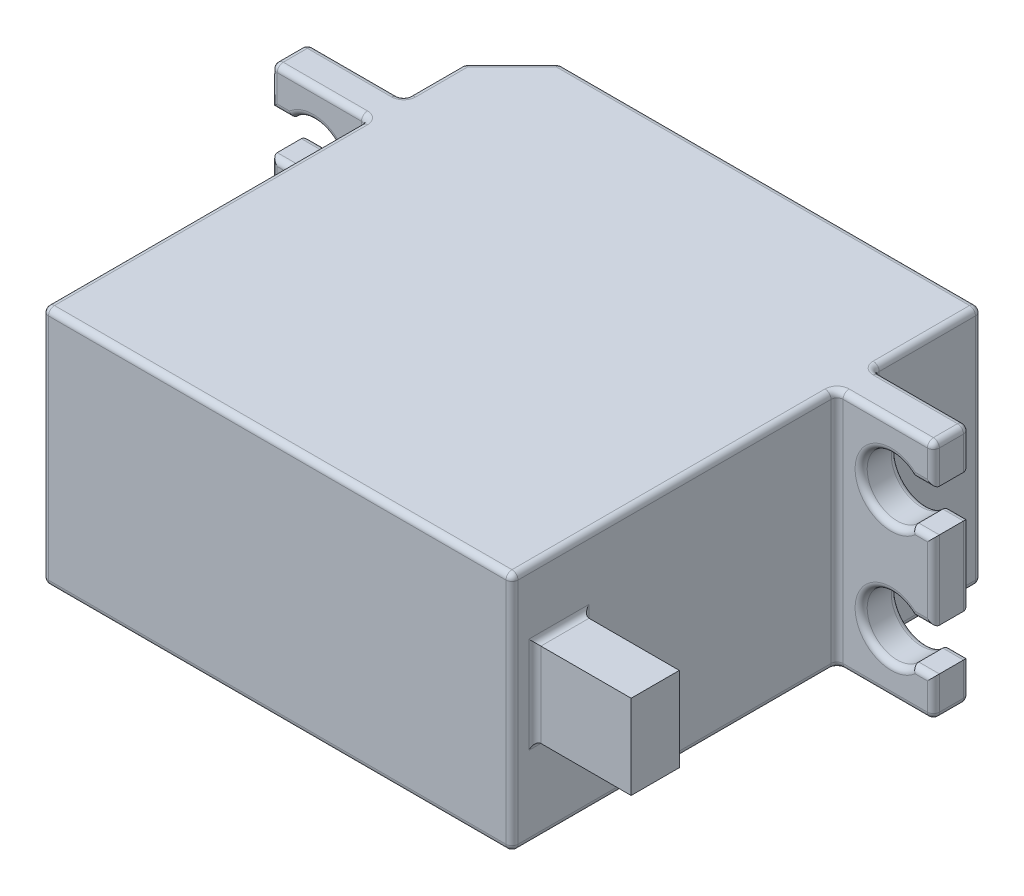
SolidWorks part; units mm, degrees
ref_plane "Plan de face" through (0, 0, 0) normal (0, 0, 1) x (1, 0, 0)
ref_plane "Plan de dessus" through (0, 0, 0) normal (0, 1, 0) x (1, 0, 0)
ref_plane "Plan de droite" through (0, 0, 0) normal (1, 0, 0) x (0, 0, -1)
sketch "Esquisse1" plane through (0, 0, 0) normal (0, 1, 0) x (1, 0, 0)
  line L0 (0, 35) -> (4, 39)
  line L1 (0, 0) -> (39, 0)
  line L2 (0, 0) -> (0, 35)
  line L3 (4, 39) -> (39, 39)
  line L4 (39, 0) -> (39, 39)
  dimension "D1" = 39
  dimension "D2" = 39
extrude "Boss.-Extru.1" add sketch "Esquisse1" along normal blind 20
sketch "Esquisse2" plane through (0, 0, 0) normal (-1, 0, 0) x (0, 0, 1)
  line L0 (-35, 0) -> (0, 0) construction
  line L1 (-30, 0) -> (-27, 0)
  line L2 (-30, 0) -> (-30, 20)
  line L3 (-30, 20) -> (-27, 20)
  line L4 (-27, 0) -> (-27, 20)
  line L5 (-35, 20) -> (0, 20) construction
  line L6 (0, 20) -> (0, 0) construction
  dimension "D1" = 3
  dimension "D2" = 27
extrude "Boss.-Extru.2" add sketch "Esquisse2" along normal blind 8 and the other way blind 47
sketch "Esquisse3" plane through (0, 0, -30) normal (0, 0, -1) x (-1, 0, 0)
  line L0 (8, 20) -> (8, 0) construction
  line L1 (0, 0) -> (8, 0) construction
  line L2 (0, 20) -> (8, 20) construction
  line L4 (6.2854, 3.25) -> (8, 3.25)
  line L5 (6.2854, 13.25) -> (8, 13.25)
  line L6 (6.2854, 6.75) -> (8, 6.75)
  line L7 (8, 3.25) -> (8, 6.75)
  line L9 (6.2854, 16.75) -> (8, 16.75)
  line L10 (8, 13.25) -> (8, 16.75)
  arc A0 (6.2854, 6.75) -> (6.2854, 3.25) centre (4.5, 5) ccw
  arc A1 (6.2854, 16.75) -> (6.2854, 13.25) centre (4.5, 15) ccw
  dimension "D1" = 5
  dimension "D2" = 5
  dimension "D3" = 3.5
  dimension "D4" = 3.5
  dimension "D5" = 5
  dimension "D6" = 5
  dimension "D8" = 1.75
  dimension "D9" = 1.75
extrude "Enlèv. mat.-Extru.1" cut sketch "Esquisse3" against normal blind 8
sketch "Esquisse4" plane through (0, 0, -30) normal (0, 0, -1) x (-1, 0, 0)
  line L0 (-47, 20) -> (-39, 20) construction
  line L1 (-47, 0) -> (-39, 0) construction
  line L2 (-47, 20) -> (-47, 0) construction
  line L3 (-39, 20) -> (-39, 0) construction
  line L4 (-47, 3.25) -> (-45.2854, 3.25)
  line L5 (-47, 3.25) -> (-47, 6.75)
  line L6 (-47, 6.75) -> (-45.2854, 6.75)
  line L8 (-45.2854, 13.25) -> (-47, 13.25)
  line L10 (-45.2854, 16.75) -> (-47, 16.75)
  line L11 (-47, 13.25) -> (-47, 16.75)
  arc A0 (-45.2854, 3.25) -> (-45.2854, 6.75) centre (-43.5, 5) ccw
  arc A1 (-45.2854, 13.25) -> (-45.2854, 16.75) centre (-43.5, 15) ccw
  dimension "D1" = 5
  dimension "D2" = 5
  dimension "D3" = 5
  dimension "D4" = 5
  dimension "D5" = 3.5
  dimension "D6" = 3.5
  dimension "D8" = 1.75
  dimension "D9" = 1.75
extrude "Enlèv. mat.-Extru.2" cut sketch "Esquisse4" against normal blind 8
sketch "Esquisse6" plane through (0, 0, -39) normal (0, 0, -1) x (-1, 0, 0)
  line L0 (-39, 20) -> (-4, 20) construction
  line L1 (-39, 20) -> (-39, 0) construction
  circle A0 centre (-29, 10) radius 6
  dimension "D1" = 12
  dimension "D2" = 10
  dimension "D3" = 10
extrude "Boss.-Extru.3" add sketch "Esquisse6" along normal blind 1
sketch "Esquisse7" plane through (0, 0, -40) normal (0, 0, -1) x (-1, 0, 0)
  line L0 (-39, 20) -> (-4, 20) construction
  line L1 (-39, 20) -> (-39, 0) construction
  circle A0 centre (-29, 10) radius 3
  dimension "D1" = 10
  dimension "D2" = 10
  dimension "D3" = 6
extrude "Boss.-Extru.4" add sketch "Esquisse7" along normal blind 4
sketch "Esquisse8" plane through (39, 0, 0) normal (1, 0, 0) x (0, 0, -1)
  line L1 (5.8966, 7.3034) -> (1.8966, 7.3034)
  line L2 (5.8966, 7.3034) -> (5.8966, 14.3034)
  line L3 (5.8966, 14.3034) -> (1.8966, 14.3034)
  line L4 (1.8966, 7.3034) -> (1.8966, 14.3034)
  dimension "D1" = 7
  dimension "D2" = 4
extrude "Boss.-Extru.5" add sketch "Esquisse8" along normal blind 8
fillet "Congé1" radius 0.5 77 edges at (0, 10, 0) (19.5, 20, 0) (0, 20, -13.5) (-8, 20, -28.5) (2, 20, -37) (47, 20, -28.5) (19.5, 0, 0) (47, 0, -28.5) (2, 0, -37) (-8, 0, -28.5) (0, 0, -13.5) (39, 0, -34.5) (39, 20, -34.5) (0, 10, -35) (0, 20, -32.5) (0, 0, -32.5) (35, 10, -39) (39, 10, -39) (21.5, 20, -39) (4, 10, -39) (21.5, 0, -39) (39, 14.3034, -3.8966) (39, 10.8034, -1.8966) (39, 7.3034, -3.8966) (39, 10.8034, -5.8966) (39, 10, 0) (39, 20, -13.5) (39, 0, -13.5) (-2, 5, -30) (-7.1427, 3.25, -30) (-8, 1.625, -30) (-4, 0, -30) (0, 10, -30) (-4, 20, -30) (-8, 18.375, -30) (-7.1427, 16.75, -30) (-2, 15, -30) (-7.1427, 13.25, -30) (-8, 10, -30) (-7.1427, 6.75, -30) (-8, 10, -27) (-7.1427, 13.25, -27) (-2, 15, -27) (-7.1427, 16.75, -27) (-8, 18.375, -27) (-4, 20, -27) (0, 10, -27) (-4, 0, -27) (-8, 1.625, -27) (-7.1427, 3.25, -27) (-2, 5, -27) (-7.1427, 6.75, -27) (41, 5, -27) (46.1427, 3.25, -27) (47, 1.625, -27) (43, 0, -27) (39, 10, -27) (43, 20, -27) (47, 18.375, -27) (46.1427, 16.75, -27) (41, 15, -27) (46.1427, 13.25, -27) (47, 10, -27) (46.1427, 6.75, -27) (47, 10, -30) (46.1427, 13.25, -30) (41, 15, -30) (46.1427, 16.75, -30) (47, 18.375, -30) (43, 20, -30) (39, 10, -30) (43, 0, -30) (47, 1.625, -30) (46.1427, 3.25, -30) (41, 5, -30) (46.1427, 6.75, -30) (23, 10, -40)
